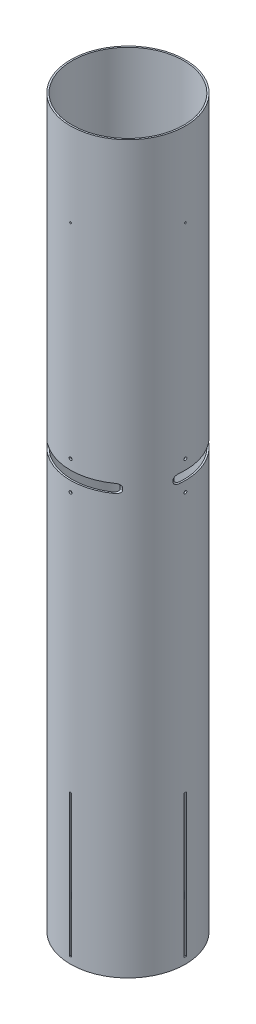
SolidWorks part; units mm, degrees
material "A-Glass Fiber"
ref_plane "Front Plane" through (0, 0, 0) normal (0, 0, 1) x (1, 0, 0)
ref_plane "Top Plane" through (0, 0, 0) normal (0, 1, 0) x (1, 0, 0)
ref_plane "Right Plane" through (0, 0, 0) normal (1, 0, 0) x (0, 0, -1)
sketch "Sketch1" plane through (0, 0, 0) normal (0, 1, 0) x (1, 0, 0)
  circle A0 centre (0, 0) radius 76.2
  circle A1 centre (0, 0) radius 78.359
  dimension "D1" = 152.4
  dimension "D2" = 156.718
extrude "Boss-Extrude1" add sketch "Sketch1" along normal blind 990.6
ref_plane "Plane1" through (0, 0, 0) normal (0.7071, 0, 0.7071) x (0.7071, 0, -0.7071)
ref_axis "Axis1" through (0, 990.6, 0) along (0, -1, 0)
sketch "Sketch2" plane through (0, 0, 0) normal (1, 0, 0) x (0, 0, -1)
  line L0 (0, 0) -> (0, 8.89)
  line L1 (1.5875, 8.89) -> (-1.5875, 8.89)
  line L2 (1.5875, 8.89) -> (1.5875, 203.2)
  line L3 (1.5875, 203.2) -> (-1.5875, 203.2)
  line L4 (-1.5875, 8.89) -> (-1.5875, 203.2)
  line L5 (1.5875, 8.89) -> (-1.5875, 203.2) construction
  line L6 (1.5875, 203.2) -> (-1.5875, 8.89) construction
  line L7 (78.359, 990.6) -> (-78.359, 990.6) construction
  line L8 (78.359, 990.6) -> (-78.359, 990.6)
  line L9 (0, 990.6) -> (0, 597.4705)
  line L10 (-78.359, 0) -> (78.359, 0) construction
  circle A0 centre (0, 597.4705) radius 2
  circle A1 centre (0, 876.3) radius 1.0922
  circle A2 centre (0, 557.7789) radius 2
  point P0 (0, 106.045)
  dimension "D4" = 4
  dimension "D6" = 2.1844
  dimension "D8" = 4
  dimension "D1" = 3.175
  dimension "D2" = 194.31
  dimension "D5" = 597.4705
  dimension "D3" = 203.2
  dimension "D7" = 114.3
  dimension "D9" = 39.6916
extrude "Fin Slots" cut sketch "Sketch2" against normal through all contours L4 L1 L2 L3 region at (0, 106.045, 0)
pattern_circular "CirPattern1" count 4 over 360 about axis through (0, 0, 0) along (0, 1, 0) of "Fin Slots" reverse direction yes
extrude "Cut-Extrude2" cut sketch "Sketch2<3>" against normal through all contours A0 region at (0, 598.8447, -1.3742)
sketch "Sketch2<3>" plane through (0, 0, 0) normal (1, 0, 0) x (0, 0, -1) same geometry as "Sketch2"
pattern_circular "CirPattern2" count 4 over 360 about axis through (0, 990.6, 0) along (0, -1, 0) of "Cut-Extrude2"
sketch "Sketch3" plane through (0, 0, 0) normal (0.7071, 0, 0.7071) x (0.7071, 0, -0.7071)
  line L0 (0, 0) -> (0, 127) construction
  circle A0 centre (0, 127) radius 3.175
  dimension "D1" = 6.35
  dimension "D2" = 127
extrude "Cut-Extrude3" cut sketch "Sketch3" against normal through all
ref_plane "Plane3" through (0, 583.8825, 0) normal (0, 1, 0) x (1, 0, 0)
sketch "Sketch7" plane through (0, 583.8825, 0) normal (0, 1, 0) x (1, 0, 0)
  line L0 (0, 0) -> (-76.8534, -15.2871)
  line L1 (0, 0) -> (0, 93.232) construction
  line L2 (0, 0) -> (-25.1877, 74.2005)
  line L3 (-78.359, 0) -> (0, 0) construction
  arc A0 (-78.3335, 2) -> (-78.3335, -2) centre (0, 0) ccw construction
  circle A1 centre (0, 0) radius 76.2 construction
  circle A2 centre (0, 0) radius 78.359
  circle A3 centre (0, 0) radius 78.359
  circle A4 centre (0, 0) radius 76.2
  circle A5 centre (0, 0) radius 78.359 construction
  arc A6 (2, 78.3335) -> (-2, 78.3335) centre (0, 0) ccw construction
  arc A7 (-78.3335, 2) -> (-78.3335, -2) centre (0, 0) ccw
  arc A8 (2, 78.3335) -> (-2, 78.3335) centre (0, 0) ccw
  dimension "D1" = 82.5
  dimension "D3" = 11.25
  dimension "D2" = 0
extrude "Cut-Extrude4" [suppressed] cut sketch "Sketch7" against normal blind 12.065
pattern_circular "CirPattern3" [suppressed] count 3 over 360 about axis through (0, 990.6, 0) along (0, -1, 0) of bodies 107
extrude "Shear Screw Holes" cut sketch "Sketch2<4>" against normal through all contours L9 A1 | L9 A1 | A2 region at (0, 876.3, -0.4635) region at (0, 876.3, 0.4635)
sketch "Sketch2<4>" plane through (0, 0, 0) normal (1, 0, 0) x (0, 0, -1) same geometry as "Sketch2"
pattern_circular "Shear Screw Pattern" count 4 over 360 about axis through (0, 990.6, 0) along (0, -1, 0) of "Shear Screw Holes"
sketch "Sketch8" plane through (0, 0, 0) normal (1, 0, 0) x (0, 0, -1)
  line L6 (-78.359, 555.7789) -> (-78.359, 203.2) construction
  line L7 (-78.359, 583.8825) -> (-63.6753, 583.8825)
  line L8 (-78.359, 583.8825) -> (-78.359, 571.8175)
  line L9 (-78.359, 571.8175) -> (-63.6753, 571.8175)
  line L10 (-58.9128, 579.12) -> (-58.9128, 576.58)
  line L11 (76.2, 990.6) -> (-76.2, 990.6) construction
  arc A2 (-63.6753, 571.8175) -> (-58.9128, 576.58) centre (-63.6753, 576.58) ccw
  arc A3 (-63.6753, 583.8825) -> (-58.9128, 579.12) centre (-63.6753, 579.12) cw
  point P24 (-58.9128, 577.85)
  dimension "D7" = 4.7625
  dimension "D5" = 19.4462
  dimension "D6" = 12.065
  dimension "D8" = 412.75
extrude "Cut-Extrude5" cut sketch "Sketch8" against normal through all both and the other way through all
pattern_circular "CirPattern4" count 3 over 360 about axis through (0, 990.6, 0) along (0, -1, 0) of "Cut-Extrude5"
equation "\"D1@Boss-Extrude1\" = \"Aft_Section_Length\""
equation "\"AB_Coupler_OD_Length\"= 1in"
equation "\"AB_Coupling_Section_Length\"= 0.375in"
equation "\"AB_Coupler_Length\"= \"AB_Coupler_OD_Length\" + \"AB_Coupling_Section_Length\" * 2"
equation "\"AB_Coupler_Num_Screws\"= 4"
equation "\"AB_Coupling_Screw_Diameter\"= 0.15748in"
equation "\"Aft_Section_Length\"= 39in"
equation "\"D4@Sketch2\"=\"AB_Coupling_Screw_Diameter\""
equation "\"D1@CirPattern2\"=\"AB_Coupler_Num_Screws\""
equation "\"Rail_Nut_From_Bottom\"= 5in"
equation "\"Rail_Nut_Diam\"= 0.25in"
equation "\"D1@Sketch3\"=\"Rail_Nut_Diam\""
equation "\"D2@Sketch3\"=\"Rail_Nut_From_Bottom\""
equation "\"AB_BKHD_Thickness\"= 0.375in"
equation "\"AB_Mount_From_Bottom\"= 23.175in"
equation "\"Cutout_Angle\"= 80"
equation "\"Shear_Screw_Diameter\"= 0.086in"
equation "\"D6@Sketch2\"=\"Shear_Screw_Diameter\""
equation "\"Shear_Screw_Coupler_Location\"= 4.5in"
equation "\"D7@Sketch2\"=\"Shear_Screw_Coupler_Location\""
equation "\"Bodytube_OD\"= 6.17in"
equation "\"Bodytube_ID\"= 5.998in"
equation "\"Motor_OD\"= 4in"
equation "\"Fwd_Tube_Length\"= 40in"
equation "\"Mid_Tube_Length\"= 1in"
equation "\"Mid_Coupler_Length\"= 13in"
equation "\"AB_Paddle_Height\"= 0.375in"
equation "\"Num_Cutouts\"= 3"
equation "\"AB_Coupler_OD\"= 6.17in"
equation "\"AB_Coupler_ID\"= 5.75in"
equation "\"AB_Coupler_Surface_Diameter\"= 5.998in"
equation "\"AB_Central_Bushing_Length\"= .4724in"
equation "\"Lead_Screw_Dist\"= 3.4in"
equation "\"Lead_Screw_Diam\"= 0.386in"
equation "\"Lead_Screw_Length\"= (\"Mid_Coupler_Length\" + 2*0.375in + 2*0.5in)"
equation "\"Paddle_Pin_Offset\"= .25in"
equation "\"Paddle_Pin_Radius\"= 2.25in"
equation "\"SS_Paddle_Pin_Radius\"= 2.25*0.66in"
equation "\"Paddle_Gear_OD\"= 3.2in"
equation "\"Drive_Gear_OD\"= 1.7in"
equation "\"Fwd_BKHD_From_Top\"= 18in"
equation "\"Fin_Thickness\"= .118in"
equation "\"Guiderail_Cutout_Diameter\"= 1.5in"
equation "\"DB9_Hole_Dist\"= 25mm"
equation "\"DB9_Relief_Width\"= 0.47in"
equation "\"DB9_Relief_Hole_Offset\"= 0.09in"
equation "\"Airbrakes_Wire_Hole_Dia\"= .25in"
equation "\"Airbrakes_Wire_Hole_Dist\"= 1.1in"
equation "\"Servo_Gear_Offset\"= 0.5in"
equation "\"D8@Sketch2\"=\"AB_Coupling_Screw_Diameter\""
